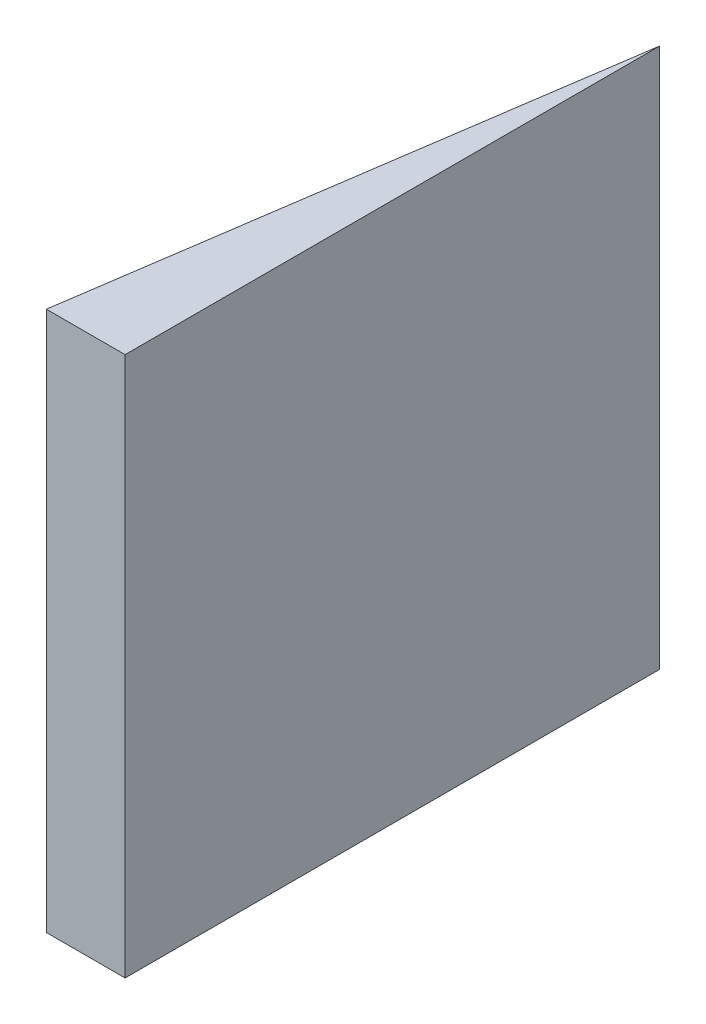
SolidWorks part; units mm, degrees
ref_plane "Front Plane" through (0, 0, 0) normal (0, 0, 1) x (1, 0, 0)
ref_plane "Top Plane" through (0, 0, 0) normal (0, 1, 0) x (1, 0, 0)
ref_plane "Right Plane" through (0, 0, 0) normal (1, 0, 0) x (0, 0, -1)
sketch "Sketch1" plane through (0, 0, 0) normal (0, 1, 0) x (1, 0, 0)
  line L0 (88.9, 603.5964) -> (0, 0)
  line L1 (0, 0) -> (88.9, 0)
  line L4 (88.9, 0) -> (88.9, 603.5964)
  dimension "D1" = 610.108
  dimension "D2" = 88.9
extrude "Boss-Extrude1" add sketch "Sketch1" along normal blind 609.6
shell "Shell1" thickness 5.08 removed face at (44.45, 304.8, -301.7982)
